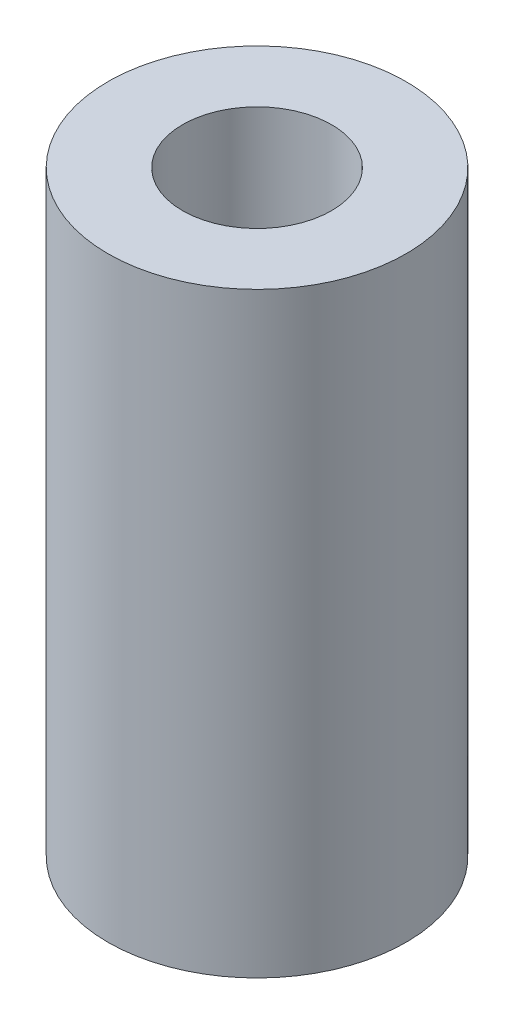
SolidWorks part; units mm, degrees
material "Brass"
ref_plane "Front Plane" through (0, 0, 0) normal (0, 0, 1) x (1, 0, 0)
ref_plane "Top Plane" through (0, 0, 0) normal (0, 1, 0) x (1, 0, 0)
ref_plane "Right Plane" through (0, 0, 0) normal (1, 0, 0) x (0, 0, -1)
sketch "Sketch1" plane through (0, 0, 0) normal (0, 1, 0) x (1, 0, 0)
  circle A0 centre (0, 0) radius 2.5
  dimension "D1" = 5
extrude "Boss-Extrude1" add sketch "Sketch1" along normal blind 10
hole_wizard "M3x0.5 Tapped Hole1" positions "Sketch2" profile "Sketch3" tap size "M3x0.5" standard "ANSI Metric" end condition through all
sketch "Sketch2" plane through (0, 10, 0) normal (0, 1, 0) x (1, 0, 0)
  point P0 (0, 0)
sketch "Sketch3" plane through (0, 10, 0) normal (1, 0, 0) x (0, 0, 1)
  line L0 (0, 0) -> (0, 10)
  line L1 (0, 10) -> (1.25, 10)
  line L2 (1.25, 10) -> (1.25, 0)
  line L5 (1.25, 0) -> (0, 0)
  line L11 (0, -6.35) -> (0, 107.95) construction
  dimension "Thru Tap Drill Dia." = 2.5
  dimension "Thru Tap Drill Depth" = 10
cosmetic thread "Hole Thread1" parameters "D2"=3
